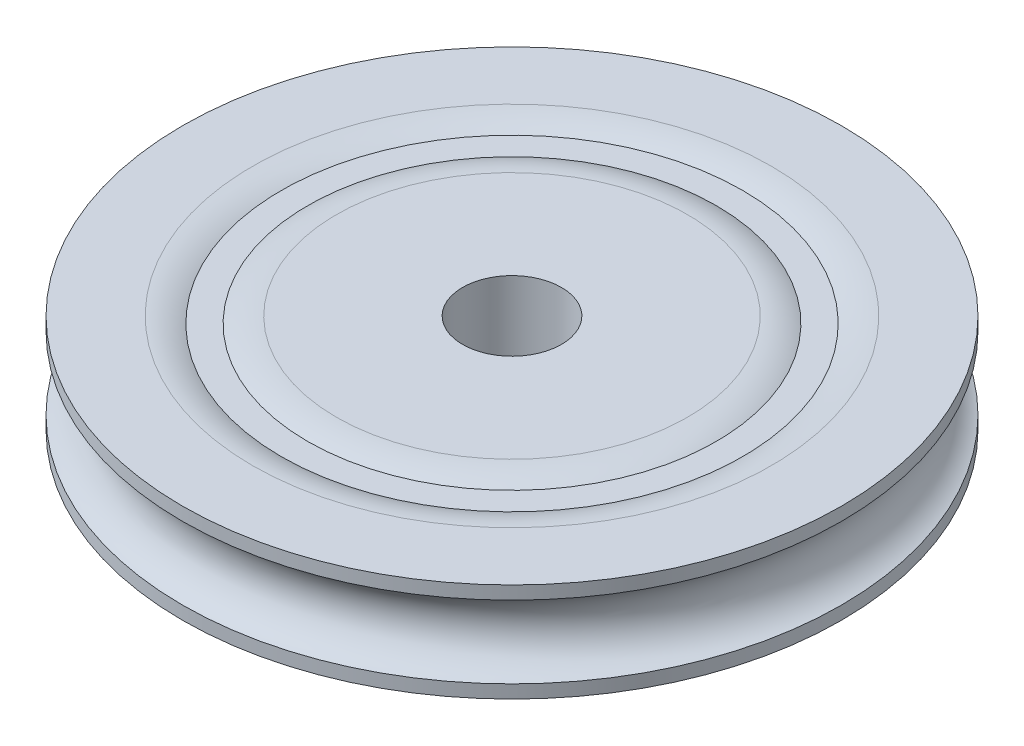
SolidWorks part; units mm, degrees
ref_plane "Front Plane" through (0, 0, 0) normal (0, 0, 1) x (1, 0, 0)
ref_plane "Top Plane" through (0, 0, 0) normal (0, 1, 0) x (1, 0, 0)
ref_plane "Right Plane" through (0, 0, 0) normal (1, 0, 0) x (0, 0, -1)
sketch "Sketch2" plane through (0, 0, 0) normal (1, 0, 0) x (0, 0, -1)
  line L0 (0, 55.4349) -> (0, -55.4349) construction
  line L1 (0, 7.5) -> (-31, 7.5)
  line L2 (-31, 7.5) -> (-31, 6.5)
  line L3 (-31, 6.5) -> (-35, 6.5)
  line L4 (-35, 6.5) -> (-35, 7.5)
  line L5 (-35, 7.5) -> (-50, 7.5)
  line L6 (-50, 7.5) -> (-50, 5.5)
  line L7 (0, 0) -> (-97.8851, 0) construction
  line L8 (0, -7.5) -> (-31, -7.5)
  line L9 (-31, -7.5) -> (-31, -6.5)
  line L10 (-31, -6.5) -> (-35, -6.5)
  line L11 (-35, -6.5) -> (-35, -7.5)
  line L12 (-35, -7.5) -> (-50, -7.5)
  line L13 (-50, -7.5) -> (-50, -5.5)
  line L14 (0, 7.5) -> (0, -7.5)
  arc A0 (-50, 5.5) -> (-50, -5.5) centre (-52, 0) cw
  point P4 (0, 0)
  point P16 (0, 0)
  point P17 (0, 0)
  dimension "D8" = 52
  dimension "D1" = 7.5
  dimension "D2" = 1
  dimension "D3" = 15
  dimension "D4" = 4
  dimension "D5" = 50
  dimension "D6" = 2
  dimension "D7" = 7.5
revolve "Revolve1" add sketch "Sketch2" angle 360 about L0
fillet "Fillet1" radius 10 1 edges at (0, 7.5, 35)
fillet "Fillet2" radius 10 1 edges at (0, 7.5, 31)
fillet "Fillet3" radius 10 1 edges at (0, -7.5, 35)
fillet "Fillet4" radius 10 1 edges at (0, -7.5, 31)
sketch "Sketch3" plane through (0, -7.5, 0) normal (0, -1, 0) x (1, 0, 0)
  circle A0 centre (0, 0) radius 7.5
  dimension "D1" = 15
extrude "Cut-Extrude1" cut sketch "Sketch3" against normal through all
